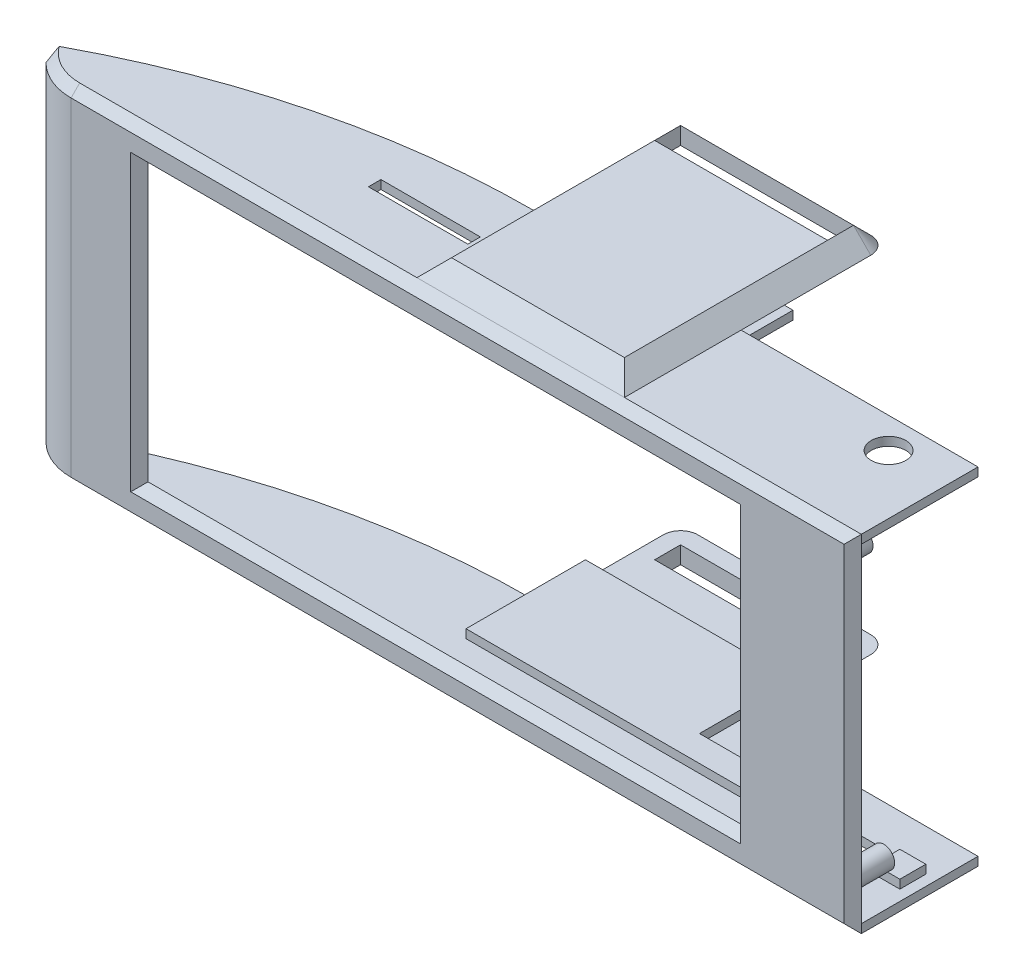
SolidWorks part; units mm, degrees
material "PLA"
ref_plane "Front Plane" through (0, 0, 0) normal (0, 0, 1) x (1, 0, 0)
ref_plane "Top Plane" through (0, 0, 0) normal (0, 1, 0) x (1, 0, 0)
ref_plane "Right Plane" through (0, 0, 0) normal (1, 0, 0) x (0, 0, -1)
sketch "Sketch1" plane through (101441.594, 0, 0) normal (0, 0, 1) x (-1, 0, 0)
  line L1 (101382.549, 35) -> (101451.049, 35)
  line L2 (101382.549, 35) -> (101382.549, 3)
  line L3 (101382.549, 3) -> (101451.049, 3)
  line L8 (101458.949, 39) -> (101368.549, 39)
  line L9 (101458.949, -1) -> (101458.949, 39)
  line L10 (101368.549, -1) -> (101458.949, -1)
  line L11 (101368.549, 39) -> (101368.549, -1)
  line L12 (101451.049, 35) -> (101451.049, 3)
  dimension "D2" = 68.5
  dimension "D3" = 14
  dimension "D4" = 4
  dimension "D5" = 4
  dimension "D6" = 90.4
  dimension "D1" = 40
extrude "Boss-Extrude1" add sketch "Sketch1" along normal blind 1
sketch "Sketch2" plane through (0, 0, 0) normal (0, 0, -1) x (-1, 0, 0)
  line L0 (-73.0451, 1) -> (17.3549, 1) construction
  line L1 (17.3549, -39) -> (-73.0451, -39) construction
  line L2 (-73.0451, -39) -> (-73.0451, 1) construction
  circle A0 centre (-70.1451, -2.5) radius 1.25
  circle A1 centre (-70.1451, -35.5) radius 1.25
  circle A2 centre (14.3549, -2.5) radius 1.25
  circle A3 centre (14.3549, -35.5) radius 1.25
  dimension "D4" = 2.5
  dimension "D1" = 3.5
  dimension "D2" = 3.5
  dimension "D3" = 2.9
  dimension "D5" = 2
extrude "Boss-Extrude2" add sketch "Sketch2" along normal blind 3
sketch "Sketch3" plane through (0, 1, 0) normal (0, 1, 0) x (1, 0, 0)
  line L0 (73.0451, 0) -> (-17.3549, 0) construction
  line L1 (-17.3549, -1) -> (-17.3549, 0) construction
  line L2 (-22.3549, 2.6834) -> (-22.3549, 1.101)
  line L3 (-17.3549, -1) -> (-17.3549, 0)
  arc A0 (-17.3549, 0) -> (-22.3549, 2.6834) centre (-17.3549, 6) cw
  arc A1 (-17.3549, -1) -> (-22.3549, 1.101) centre (-17.3549, 6) cw
  arc A3 (-17.3549, -1) -> (-23.1883, 2.1306) centre (-17.3549, 6) cw construction
  dimension "D1" = 6
  dimension "D2" = 5
extrude "Boss-Extrude3" add sketch "Sketch3" against normal through all separate body
chamfer "Chamfer1" distance 1 angle 45 2 edges at (-20.0667, 1, 0.4534) (-20.0667, -39, 0.4534)
chamfer "Chamfer2" distance 1 angle 45 7 edges at (24.7951, -3, 1) (-9.4549, -19, 1) (24.7951, -35, 1) (59.0451, -19, 1) (27.8451, -39, 1) (73.0451, -19, 1) (27.8451, 1, 1)
ref_plane "Plane1" through (0, -39, 0) normal (0, 1, 0) x (1, 0, 0)
ref_plane "Plane2" through (0, 1, 0) normal (0, 1, 0) x (1, 0, 0)
sketch "Sketch6" plane through (0, 1, 0) normal (0, 1, 0) x (1, 0, 0)
  line L0 (73.0451, 0) -> (-17.3549, 0) construction
  line L1 (71.8188, 0) -> (61.8388, 0)
  line L2 (71.8188, 0) -> (71.8188, 13.9185)
  line L3 (71.8188, 13.9185) -> (61.8388, 13.9185)
  line L4 (61.8388, 0) -> (61.8388, 13.9185)
  line L5 (29.764, 0) -> (-0.962, 0)
  line L6 (29.764, 0) -> (29.764, 11.5588)
  line L7 (29.764, 11.5588) -> (-0.962, 11.5588)
  line L8 (-0.962, 0) -> (-0.962, 11.5588)
  line L10 (19.6612, 5.9892) -> (7.4739, 5.9892)
  line L11 (19.6612, 5.9892) -> (19.6612, 7.9655)
  line L12 (19.6612, 7.9655) -> (7.4739, 7.9655)
  line L13 (7.4739, 5.9892) -> (7.4739, 7.9655)
  circle A0 centre (66.8561, 9.9375) radius 1.9758
extrude "Boss-Extrude4" add sketch "Sketch6" against normal blind 1
sketch "Sketch8" plane through (0, 0, 0) normal (0, -1, 0) x (1, 0, 0)
  line L0 (29.764, 0) -> (29.764, -11.5588) construction
  line L1 (29.764, -8.6788) -> (24.764, -8.6788)
  line L2 (29.764, -8.6788) -> (29.764, -5.6788)
  line L3 (29.764, -5.6788) -> (24.764, -5.6788)
  line L4 (24.764, -8.6788) -> (24.764, -5.6788)
  line L5 (29.764, -11.5588) -> (-0.962, -11.5588) construction
  dimension "D1" = 5.88
  dimension "D2" = 3
  dimension "D3" = 5
extrude "Boss-Extrude6" add sketch "Sketch8" along normal blind 1
sketch "Sketch9" plane through (0, -39, 0) normal (0, 1, 0) x (1, 0, 0)
  line L1 (67.2061, 8.8062) -> (63.1589, 8.8062)
  line L2 (67.2061, 8.8062) -> (67.2061, 6.8122)
  line L3 (67.2061, 6.8122) -> (63.1589, 6.8122)
  line L4 (29.764, 0) -> (29.764, 11.5588)
  line L5 (29.764, 11.5588) -> (-0.962, 11.5588)
  line L6 (-0.962, 11.5588) -> (-0.962, 0)
  line L7 (-0.962, 0) -> (29.764, 0)
  line L8 (29.764, 0) -> (29.764, 11.5588)
  line L9 (29.764, 11.5588) -> (-0.962, 11.5588)
  line L10 (-0.962, 11.5588) -> (-0.962, 0)
  line L11 (-0.962, 0) -> (29.764, 0)
  line L12 (71.8188, 0) -> (71.8188, 13.9185)
  line L13 (61.8388, 0) -> (71.8188, 0)
  line L14 (61.8388, 13.9185) -> (61.8388, 0)
  line L15 (71.8188, 13.9185) -> (61.8388, 13.9185)
  line L16 (71.8188, 0) -> (71.8188, 13.9185)
  line L17 (61.8388, 0) -> (71.8188, 0)
  line L18 (61.8388, 13.9185) -> (61.8388, 0)
  line L19 (71.8188, 13.9185) -> (61.8388, 13.9185)
  line L20 (63.1589, 8.8062) -> (63.1589, 6.8122)
  dimension "D1" = 0
  dimension "D2" = 0
extrude "Boss-Extrude7" add sketch "Sketch9" along normal blind 1
sketch "Sketch10" plane through (0, -38, 0) normal (0, 1, 0) x (1, 0, 0)
  line L0 (71.8188, 0) -> (71.8188, 13.9185) construction
  line L1 (71.8188, 5.6785) -> (68.8188, 5.6785)
  line L2 (71.8188, 5.6785) -> (71.8188, 8.6785)
  line L3 (71.8188, 8.6785) -> (68.8188, 8.6785)
  line L4 (29.764, 5.6788) -> (29.764, 8.6788)
  line L5 (24.764, 5.6788) -> (29.764, 5.6788)
  line L6 (24.764, 8.6788) -> (24.764, 5.6788)
  line L7 (29.764, 8.6788) -> (24.764, 8.6788)
  line L8 (29.764, 5.6788) -> (29.764, 8.6788)
  line L9 (24.764, 5.6788) -> (29.764, 5.6788)
  line L10 (24.764, 8.6788) -> (24.764, 5.6788)
  line L11 (29.764, 8.6788) -> (24.764, 8.6788)
  line L12 (68.8188, 5.6785) -> (68.8188, 8.6785)
  line L13 (71.8188, 13.9185) -> (61.8388, 13.9185) construction
  dimension "D2" = 8.24
  dimension "D3" = 3
  dimension "D4" = 3
  dimension "D1" = 0
extrude "Boss-Extrude8" add sketch "Sketch10" along normal blind 1
sketch "Sketch11" plane through (29.764, 0, 0) normal (1, 0, 0) x (0, 0, -1)
  line L8 (11.5588, 1) -> (0, 1)
  line L9 (0, 1) -> (0, 0)
  line L10 (0, 0) -> (5.6788, 0)
  line L11 (5.6788, 0) -> (5.6788, -1)
  line L12 (5.6788, -1) -> (8.6788, -1)
  line L13 (8.6788, -1) -> (8.6788, 0)
  line L14 (8.6788, 0) -> (11.5588, 0)
  line L15 (11.5588, 0) -> (11.5588, 1)
  line L16 (11.5588, 1) -> (0, 1)
  line L17 (0, 1) -> (0, 0)
  line L18 (0, 0) -> (5.6788, 0)
  line L19 (5.6788, 0) -> (5.6788, -1)
  line L20 (5.6788, -1) -> (8.6788, -1)
  line L21 (8.6788, -1) -> (8.6788, 0)
  line L22 (8.6788, 0) -> (11.5588, 0)
  line L23 (11.5588, 0) -> (11.5588, 1)
  dimension "D1" = 0
extrude "Boss-Extrude9" add sketch "Sketch11" along normal up to vertex (32.0748 mm away) up to point (61.8388, 1, 0)
sketch "Sketch12" plane through (29.764, 0, 0) normal (1, 0, 0) x (0, 0, -1)
  line L8 (0, -39) -> (11.5588, -39)
  line L9 (11.5588, -39) -> (11.5588, -38)
  line L10 (11.5588, -38) -> (8.6788, -38)
  line L11 (8.6788, -38) -> (8.6788, -37)
  line L12 (8.6788, -37) -> (5.6788, -37)
  line L13 (5.6788, -37) -> (5.6788, -38)
  line L14 (5.6788, -38) -> (0, -38)
  line L15 (0, -38) -> (0, -39)
  line L16 (0, -39) -> (11.5588, -39)
  line L17 (11.5588, -39) -> (11.5588, -38)
  line L18 (11.5588, -38) -> (8.6788, -38)
  line L19 (8.6788, -38) -> (8.6788, -37)
  line L20 (8.6788, -37) -> (5.6788, -37)
  line L21 (5.6788, -37) -> (5.6788, -38)
  line L22 (5.6788, -38) -> (0, -38)
  line L23 (0, -38) -> (0, -39)
  dimension "D1" = 0
extrude "Boss-Extrude10" add sketch "Sketch12" along normal up to vertex (32.0748 mm away) up to point (61.8388, -39, -13.9185)
sketch "Sketch13" plane through (0, -39, 0) normal (0, -1, 0) x (1, 0, 0)
  line L1 (-22.3549, -5.5334) -> (-22.3549, -2.6834) construction
  line L2 (-17.3549, 0) -> (-0.962, 0) construction
  line L3 (-17.3549, 0) -> (-0.962, 0)
  line L4 (-0.962, -11.5588) -> (-0.962, 0) construction
  line L5 (-0.962, -11.5588) -> (-0.962, 0)
  arc A0 (-22.3549, -5.5334) -> (-0.962, -11.5588) centre (15.2842, 87.1127) ccw
  arc A2 (-17.3549, 0) -> (-22.3549, -2.6834) centre (-17.3549, -6) ccw construction
  arc A3 (-17.3549, 0) -> (-22.3549, -2.6834) centre (-17.3549, -6) ccw
  arc A4 (-22.3549, -2.6834) -> (-23.2939, -5.1463) centre (-17.3549, -6) ccw
  arc A5 (-22.3549, -5.5334) -> (-23.2939, -5.1463) centre (15.2842, 87.1127) cw
  dimension "D1" = 100
  dimension "D2" = 2.85
extrude "Boss-Extrude11" add sketch "Sketch13" against normal up to surface (1 mm away) up to face at (54.6666, -38, -7.9669)
sketch "Sketch14" plane through (0, 1, 0) normal (0, 1, 0) x (1, 0, 0)
  line L0 (-0.962, 0) -> (-17.3549, 0)
  line L1 (-0.962, 11.5588) -> (-0.962, 0)
  arc A0 (-22.3549, 2.6834) -> (-17.3549, 0) centre (-17.3549, 6) ccw construction
  arc A1 (-23.2939, 5.1463) -> (-22.3549, 2.6834) centre (-17.3549, 6) ccw construction
  arc A2 (-0.962, 11.5588) -> (-23.2939, 5.1463) centre (15.2842, -87.1127) ccw construction
  arc A3 (-22.3549, 2.6834) -> (-17.3549, 0) centre (-17.3549, 6) ccw
  arc A4 (-23.2939, 5.1463) -> (-22.3549, 2.6834) centre (-17.3549, 6) ccw
  arc A5 (-0.962, 11.5588) -> (-23.2939, 5.1463) centre (15.2842, -87.1127) ccw
extrude "Boss-Extrude12" add sketch "Sketch14" against normal up to surface (1 mm away) up to face at (43.3014, 0, -7.1788)
sketch "Sketch15" plane through (0, 1, 0) normal (0, 1, 0) x (1, 0, 0)
  line L0 (61.8388, 13.9185) -> (61.8388, 11.5588) construction
  line L1 (61.8388, 13.9185) -> (61.8388, 11.5588)
  line L4 (61.8388, 13.9185) -> (-0.962, 11.5588)
  line L5 (-0.962, 11.5588) -> (61.8388, 11.5588)
extrude "Boss-Extrude13" add sketch "Sketch15" against normal up to surface (1 mm away) up to face at (43.3014, 0, -7.1788)
sketch "Sketch16" plane through (0, -39, 0) normal (0, -1, 0) x (1, 0, 0)
  line L0 (-0.962, -11.5588) -> (61.8388, -13.9185) construction
  line L1 (-0.962, -11.5588) -> (61.8388, -13.9185)
  line L2 (61.8388, -13.9185) -> (61.8388, -11.5588) construction
  line L3 (61.8388, -11.5588) -> (-0.962, -11.5588) construction
  line L4 (61.8388, -13.9185) -> (61.8388, -11.5588)
  line L5 (61.8388, -11.5588) -> (-0.962, -11.5588)
extrude "Boss-Extrude14" add sketch "Sketch16" against normal up to surface (1 mm away) up to face at (40.3303, -38, -7.289)
sketch "Sketch18" plane through (0, 1, 0) normal (0, 1, 0) x (1, 0, 0)
  line L4 (71.8188, 0) -> (71.8188, 13.9185)
  line L5 (71.8188, 13.9185) -> (61.8388, 13.9185)
  line L6 (61.8388, 13.9185) -> (-0.962, 11.5588)
  line L7 (-17.3549, 0) -> (71.8188, 0)
  line L8 (71.8188, 0) -> (71.8188, 13.9185)
  line L9 (71.8188, 13.9185) -> (61.8388, 13.9185)
  line L10 (61.8388, 13.9185) -> (-0.962, 11.5588)
  line L11 (-17.3549, 0) -> (71.8188, 0)
  arc A3 (-0.962, 11.5588) -> (-23.2939, 5.1463) centre (15.2842, -87.1127) ccw
  arc A4 (-23.2939, 5.1463) -> (-22.3549, 2.6834) centre (-17.3549, 6) ccw
  arc A5 (-22.3549, 2.6834) -> (-17.3549, 0) centre (-17.3549, 6) ccw
  arc A6 (-0.962, 11.5588) -> (-23.2939, 5.1463) centre (15.2842, -87.1127) ccw
  arc A7 (-23.2939, 5.1463) -> (-22.3549, 2.6834) centre (-17.3549, 6) ccw
  arc A8 (-22.3549, 2.6834) -> (-17.3549, 0) centre (-17.3549, 6) ccw
  dimension "D1" = 0
extrude "Cut-Extrude1" cut sketch "Sketch18" against normal blind 1
sketch "Sketch17" plane through (0, 1, 0) normal (0, 1, 0) x (1, 0, 0)
  line L0 (73.0451, 13.49) -> (73.0451, 0)
  line L2 (73.0477, 13.49) -> (21.6451, 13.49)
  line L4 (73.0451, 0) -> (-17.3549, 0)
  line L5 (71.8188, 0) -> (71.8188, 13.9185) construction
  line L11 (19.6612, 5.9892) -> (19.6612, 7.9655)
  line L12 (7.4739, 5.9892) -> (19.6612, 5.9892)
  line L13 (7.4739, 7.9655) -> (7.4739, 5.9892)
  line L14 (19.6612, 7.9655) -> (7.4739, 7.9655)
  arc A1 (21.6451, 13.49) -> (-22.211, 2.476) centre (21.6451, -79.331) ccw
  arc A3 (-22.211, 2.476) -> (-17.3549, 0) centre (-17.3549, 6) ccw
  circle A5 centre (66.8561, 9.9375) radius 1.9758
  dimension "D1" = 92.821
  dimension "D5" = 3.9517
  dimension "D6" = 6
  dimension "D2" = 1.2289
  dimension "D3" = 50.1737
  dimension "D4" = 94.0298
  dimension "D7" = 7.4739
  dimension "D8" = 19.6612
  dimension "D9" = 66.8561
  dimension "D10" = 17.3549
  dimension "D11" = 5.9892
  dimension "D12" = 7.9655
  dimension "D13" = 9.9375
extrude "Boss-Extrude15" add sketch "Sketch17" against normal blind 1 contours A1 A3 L4 L0 L2 A5 L14 L11 L12 L13 region at (30.6754, 1, -6.2222)
sketch "Sketch19" plane through (0, -39, 0) normal (0, -1, 0) x (1, 0, 0)
  line L4 (-0.962, -11.5588) -> (61.8388, -13.9185)
  line L5 (61.8388, -13.9185) -> (71.8188, -13.9185)
  line L6 (71.8188, -13.9185) -> (71.8188, 0)
  line L7 (71.8188, 0) -> (-17.3549, 0)
  line L8 (-0.962, -11.5588) -> (61.8388, -13.9185)
  line L9 (61.8388, -13.9185) -> (71.8188, -13.9185)
  line L10 (71.8188, -13.9185) -> (71.8188, 0)
  line L11 (71.8188, 0) -> (-17.3549, 0)
  arc A3 (-17.3549, 0) -> (-22.3549, -2.6834) centre (-17.3549, -6) ccw
  arc A4 (-22.3549, -2.6834) -> (-23.2939, -5.1463) centre (-17.3549, -6) ccw
  arc A5 (-23.2939, -5.1463) -> (-0.962, -11.5588) centre (15.2842, 87.1127) ccw
  arc A6 (-17.3549, 0) -> (-22.3549, -2.6834) centre (-17.3549, -6) ccw
  arc A7 (-22.3549, -2.6834) -> (-23.2939, -5.1463) centre (-17.3549, -6) ccw
  arc A8 (-23.2939, -5.1463) -> (-0.962, -11.5588) centre (15.2842, 87.1127) ccw
  dimension "D1" = 0
extrude "Cut-Extrude2" cut sketch "Sketch19" against normal blind 1
sketch "Sketch20" plane through (0, -38, 0) normal (0, -1, 0) x (1, 0, 0)
  line L3 (21.6451, -13.49) -> (73.0451, -13.49)
  line L4 (73.0451, -13.49) -> (73.0451, 0)
  line L5 (73.0451, 0) -> (-17.3549, 0)
  line L6 (21.6451, -13.49) -> (73.0451, -13.49)
  line L7 (73.0451, -13.49) -> (73.0451, 0)
  line L8 (73.0451, 0) -> (-17.3549, 0)
  line L14 (67.6677, -6.28) -> (62.6677, -6.28)
  line L15 (62.6677, -6.28) -> (62.6677, -9.28)
  line L16 (62.6677, -9.28) -> (67.6677, -9.28)
  line L17 (67.6677, -9.28) -> (67.6677, -6.28)
  arc A2 (-22.211, -2.476) -> (21.6451, -13.49) centre (21.6451, 79.331) ccw
  arc A3 (-17.3549, 0) -> (-22.211, -2.476) centre (-17.3549, -6) ccw
  arc A4 (-22.211, -2.476) -> (21.6451, -13.49) centre (21.6451, 79.331) ccw
  arc A5 (-17.3549, 0) -> (-22.211, -2.476) centre (-17.3549, -6) ccw
  dimension "D1" = 0
extrude "Boss-Extrude16" add sketch "Sketch20" along normal blind 1
sketch "Sketch21" plane through (0, -39, 0) normal (0, -1, 0) x (1, 0, 0)
  line L0 (-22.211, -2.476) -> (-22.3549, -1.101)
  line L1 (-22.3549, -1.101) -> (-22.3549, -2.6834)
  arc A0 (-22.211, -2.476) -> (-22.3549, -2.6834) centre (-17.3549, -6) ccw construction
  arc A1 (-22.211, -2.476) -> (-22.3549, -2.6834) centre (-17.3549, -6) ccw
extrude "Cut-Extrude3" cut sketch "Sketch21" against normal through all both and the other way through all
sketch "Sketch22" plane through (0, 0, -3) normal (0, 0, -1) x (-1, 0, 0)
  circle A1 centre (-70.1451, -35.5) radius 1.25
  circle A2 centre (-70.1451, -35.5) radius 1.25
  dimension "D1" = 0
extrude "Boss-Extrude17" add sketch "Sketch22" along normal blind 2.5
sketch "Sketch23" plane through (0, 1, 0) normal (0, 1, 0) x (1, 0, 0)
  line L0 (7.4739, 7.9655) -> (7.4739, 5.9892) construction
  line L1 (19.6612, 5.9892) -> (19.6612, 7.9655) construction
  line L2 (7.4739, 5.9892) -> (19.6612, 5.9892) construction
  line L3 (19.6612, 7.9655) -> (7.4739, 7.9655) construction
  line L4 (7.4739, 7.9655) -> (7.4739, 5.9892)
  line L5 (19.6612, 5.9892) -> (19.6612, 7.9655)
  line L6 (7.4739, 5.9892) -> (19.6612, 5.9892)
  line L7 (19.6612, 7.9655) -> (7.4739, 7.9655)
  circle A0 centre (66.8561, 9.9375) radius 1.9758 construction
  circle A1 centre (66.8561, 9.9375) radius 1.9758
extrude "Boss-Extrude18" add sketch "Sketch23" against normal up to surface (1 mm away) up to face at (43.3014, 0, -7.1788)
sketch "Sketch24" plane through (0, -39, 0) normal (0, -1, 0) x (1, 0, 0)
  line L0 (62.6677, -6.28) -> (62.6677, -9.28) construction
  line L1 (62.6677, -9.28) -> (67.6677, -9.28) construction
  line L2 (67.6677, -9.28) -> (67.6677, -6.28) construction
  line L3 (67.6677, -6.28) -> (62.6677, -6.28) construction
  line L4 (62.6677, -6.28) -> (62.6677, -9.28)
  line L5 (62.6677, -9.28) -> (67.6677, -9.28)
  line L6 (67.6677, -9.28) -> (67.6677, -6.28)
  line L7 (67.6677, -6.28) -> (62.6677, -6.28)
extrude "Boss-Extrude19" add sketch "Sketch24" against normal up to surface (1 mm away) up to face at (65.1677, -38, -7.78)
sketch "Sketch25" plane through (0, -39, 0) normal (0, -1, 0) x (1, 0, 0)
  line L4 (62.8337, -6.78) -> (62.8337, -8.78)
  line L5 (66.8337, -6.78) -> (62.8337, -6.78)
  line L6 (66.8337, -8.78) -> (66.8337, -6.78)
  line L7 (62.8337, -8.78) -> (66.8337, -8.78)
extrude "Cut-Extrude4" cut sketch "Sketch25" against normal up to surface (1 mm away) up to face at (25.4382, -38, -6.3168)
sketch "Sketch26" plane through (0, 1, 0) normal (0, 1, 0) x (1, 0, 0)
  line L8 (9.9839, 6.55) -> (10.7769, 6.55) construction
  line L9 (10.7769, 7.5) -> (9.9839, 7.5) construction
  line L10 (9.9839, 7.5) -> (9.9839, 6.55) construction
  line L11 (20.9835, 7.5) -> (20.9835, 6.55) construction
  line L12 (10.7769, 6.55) -> (20.1766, 6.55) construction
  line L13 (20.1766, 6.55) -> (20.9835, 6.55) construction
  line L14 (20.9835, 7.5) -> (20.1766, 7.5) construction
  line L15 (10.7769, 7.5) -> (20.1766, 7.5) construction
  line L16 (9.7339, 7.75) -> (9.7339, 6.3)
  line L17 (9.7339, 6.3) -> (10.7769, 6.3)
  line L18 (10.7769, 6.3) -> (20.1766, 6.3)
  line L19 (20.1766, 6.3) -> (21.2335, 6.3)
  line L20 (21.2335, 7.75) -> (21.2335, 6.3)
  line L21 (21.2335, 7.75) -> (20.1766, 7.75)
  line L22 (10.7769, 7.75) -> (20.1766, 7.75)
  line L23 (10.7769, 7.75) -> (9.7339, 7.75)
  circle A3 centre (66.2227, 9.9656) radius 2
  dimension "D2" = 0.25
extrude "Cut-Extrude5" cut sketch "Sketch26" against normal up to surface (1 mm away) contours L22 L23 L16 L17 L18 L19 L20 L21 | A3 region at (15.4837, 1, -7.025) region at (66.2227, 1, -9.9656) up to face at (43.3014, 0, -7.1788)
sketch "Sketch27" plane through (0, 1, 0) normal (0, 1, 0) x (1, 0, 0)
  line L0 (45.6451, 13.49) -> (45.6451, 0)
  line L1 (21.6451, 13.49) -> (45.6451, 13.49) construction
  line L2 (21.6451, 13.49) -> (21.6451, 30.49)
  line L3 (21.6451, 30.49) -> (45.6451, 30.49)
  line L4 (45.6451, 13.49) -> (45.6451, 30.49)
  line L5 (45.6451, 0) -> (21.6451, 0)
  line L6 (21.6451, 0) -> (21.6451, 13.49)
  line L8 (43.6451, 28.49) -> (23.6451, 28.49)
  line L9 (43.6451, 28.49) -> (43.6451, 25.49)
  line L10 (43.6451, 25.49) -> (23.6451, 25.49)
  line L11 (23.6451, 28.49) -> (23.6451, 25.49)
  dimension "D1" = 2
extrude "Boss-Extrude20" add sketch "Sketch27" along normal blind 2
sketch "Sketch28" plane through (0, -39, 0) normal (0, -1, 0) x (1, 0, 0)
  line L0 (23.6451, -28.49) -> (23.6451, -25.49) construction
  line L1 (43.6451, -25.49) -> (43.6451, -28.49) construction
  line L2 (23.6451, -25.49) -> (43.6451, -25.49) construction
  line L3 (43.6451, -28.49) -> (23.6451, -28.49) construction
  line L4 (21.6451, 0) -> (21.6451, -30.49)
  line L5 (45.6451, 0) -> (21.6451, 0)
  line L6 (45.6451, -30.49) -> (45.6451, 0)
  line L7 (21.6451, -30.49) -> (45.6451, -30.49)
  line L8 (21.6451, 0) -> (21.6451, -30.49)
  line L9 (45.6451, 0) -> (21.6451, 0)
  line L10 (45.6451, -30.49) -> (45.6451, 0)
  line L11 (21.6451, -30.49) -> (45.6451, -30.49)
  line L12 (23.6451, -28.49) -> (23.6451, -25.49)
  line L13 (43.6451, -25.49) -> (43.6451, -28.49)
  line L14 (23.6451, -25.49) -> (43.6451, -25.49)
  line L15 (43.6451, -28.49) -> (23.6451, -28.49)
  dimension "D1" = 0
extrude "Boss-Extrude21" add sketch "Sketch28" along normal blind 2
chamfer "Chamfer3" distance 2 angle 45 2 edges at (33.6451, -41, 0) (33.6451, 3, 0)
fillet "Fillet1" radius 2 4 edges at (21.6451, -40, -30.49) (45.6451, -40, -30.49) (21.6451, 2, -30.49) (45.6451, 2, -30.49)
chamfer "Chamfer4" distance 2 angle 45 10 edges at (21.6451, 3, -15.245) (22.2309, 3, -29.9042) (33.6451, 3, -30.49) (45.0593, 3, -29.9042) (45.6451, 3, -15.245) (21.6451, -41, -15.245) (22.2309, -41, -29.9042) (33.6451, -41, -30.49) (45.0593, -41, -29.9042) (45.6451, -41, -15.245)
sketch "Sketch29" plane through (0, -38, 0) normal (0, 1, 0) x (1, 0, 0)
  line L0 (21.6451, 13.49) -> (73.0451, 13.49) construction
  line L1 (21.6451, 13.49) -> (45.6451, 13.49) construction
  line L2 (21.6451, 13.49) -> (21.6451, 28.49) construction
  line L3 (21.6451, 13.49) -> (21.6451, 19.49)
  line L4 (45.6451, 28.49) -> (45.6451, 13.49) construction
  line L5 (45.6451, 19.49) -> (45.6451, 13.49)
  line L7 (45.6451, 19.49) -> (21.6451, 19.49)
  line L8 (45.6451, 13.49) -> (45.6451, 8.6788)
  line L9 (45.6451, 8.6788) -> (21.6451, 8.6788)
  line L10 (21.6451, 8.6788) -> (21.6451, 13.49)
  line L11 (61.8388, 8.6788) -> (24.764, 8.6788) construction
  dimension "D1" = 6
extrude "Boss-Extrude22" add sketch "Sketch29" along normal up to surface (1 mm away) up to face at (43.3014, -37, -7.1788)
sketch "Sketch30" plane through (24.764, 0, 0) normal (-1, 0, 0) x (0, 0, 1)
  line L4 (-8.6788, -38) -> (-5.6788, -38)
  line L5 (-5.6788, -38) -> (-5.6788, -37)
  line L6 (-5.6788, -37) -> (-8.6788, -37)
  line L7 (-8.6788, -37) -> (-8.6788, -38)
  line L8 (-8.6788, -38) -> (-5.6788, -38)
  line L9 (-5.6788, -38) -> (-5.6788, -37)
  line L10 (-5.6788, -37) -> (-8.6788, -37)
  line L11 (-8.6788, -37) -> (-8.6788, -38)
  dimension "D1" = 0
extrude "Boss-Extrude23" add sketch "Sketch30" along normal up to surface (3.119 mm away) up to face at (21.6451, -37.6, -13.9655)
sketch "Sketch31" plane through (0, 0, 0) normal (0, -1, 0) x (1, 0, 0)
  line L0 (45.6451, -19.49) -> (21.6451, -19.49) construction
  line L1 (21.6451, -19.49) -> (21.6451, -5.6788) construction
  line L2 (45.6451, -8.6788) -> (45.6451, -19.49) construction
  line L3 (45.6451, -19.49) -> (21.6451, -19.49)
  line L4 (21.6451, -19.49) -> (21.6451, -5.6788)
  line L5 (45.6451, -8.6788) -> (45.6451, -19.49)
  line L6 (21.6451, -5.6788) -> (45.6451, -5.6788)
  line L7 (61.8388, -5.6788) -> (24.764, -5.6788) construction
  line L8 (45.6451, -5.6788) -> (45.6451, -8.6788)
extrude "Boss-Extrude24" add sketch "Sketch31" along normal up to surface (1 mm away) up to face at (43.3014, -1, -7.1788)
